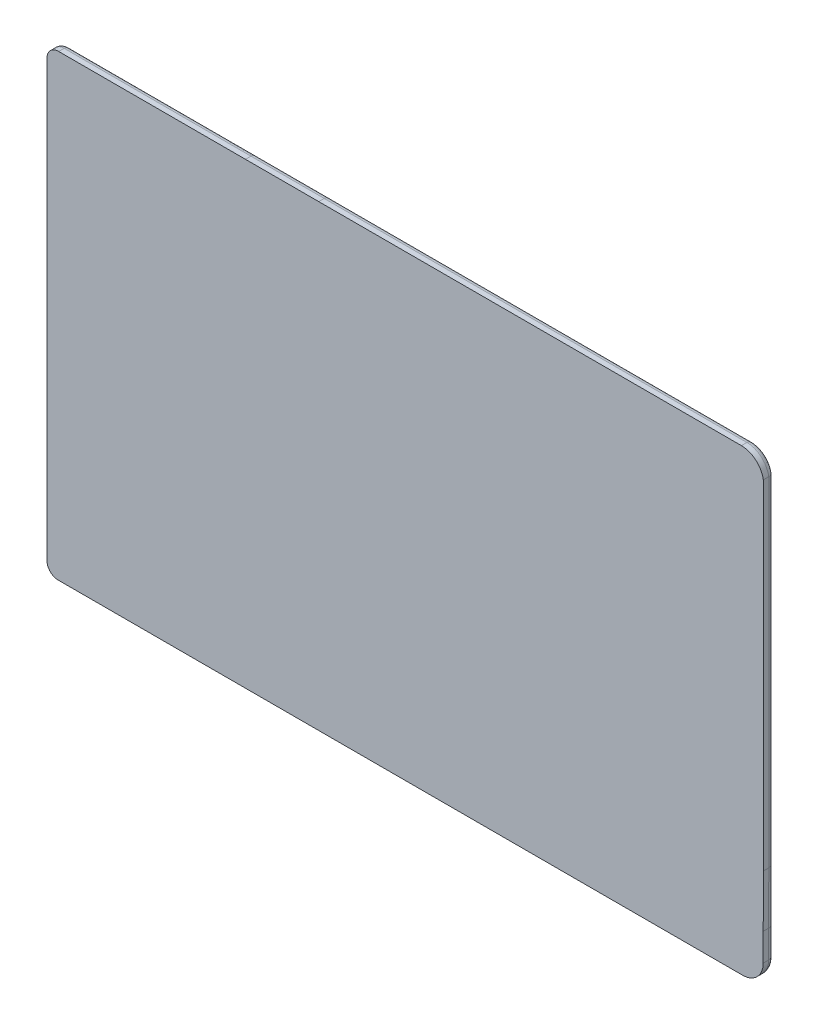
SolidWorks part; units mm, degrees
ref_plane "Front Plane" through (0, 0, 0) normal (0, 0, 1) x (1, 0, 0)
ref_plane "Top Plane" through (0, 0, 0) normal (0, 1, 0) x (1, 0, 0)
ref_plane "Right Plane" through (0, 0, 0) normal (1, 0, 0) x (0, 0, -1)
sketch "Sketch1" plane through (0, 0, 0) normal (0, 0, 1) x (1, 0, 0)
  line L58 (-23.7559, 7.1563) -> (-23.7559, 15.1458)
  line L61 (-23.7559, -4.5467) -> (-23.7559, -52.7249)
  line L66 (-23.7559, -57.433) -> (-23.7559, -64.4373)
  line L67 (-21.7197, -66.498) -> (103.2421, -66.498)
  line L69 (107.2324, -62.6937) -> (107.2324, -57.648)
  line L71 (107.2421, -48.1039) -> (107.2421, -39.782)
  line L74 (12.5461, 17.2703) -> (-21.6069, 17.2703)
  line L77 (107.2421, -33.7922) -> (107.2421, -20.0797)
  line L78 (107.2421, -4.5797) -> (107.2421, 13.8581)
  line L80 (-21.6069, 16.5996) -> (-21.6069, 16.5962)
  line L85 (25.9461, 17.2719) -> (103.2421, 17.2719)
  line L87 (107.2421, -20.0797) -> (107.2421, -4.5797)
  line L89 (107.2324, -57.648) -> (107.2421, -48.1039)
  line L90 (107.2421, -33.7922) -> (107.2421, -39.782)
  line L91 (-23.7559, -52.7249) -> (-23.7559, -57.433)
  line L92 (-23.7559, 7.1563) -> (-23.7559, -4.5467)
  line L93 (12.5461, 17.2703) -> (25.9461, 17.2719)
  arc A9 (-23.7559, 15.1458) -> (-21.6069, 17.2703) centre (-21.6313, 15.1458) cw
  arc A11 (103.2421, 17.2719) -> (107.2421, 13.8581) centre (103.2421, 13.2216) cw
  arc A13 (107.2324, -62.6937) -> (103.2421, -66.498) centre (103.4238, -62.6937) cw
  arc A15 (-23.7559, -64.4373) -> (-21.7197, -66.498) centre (-21.6951, -64.4373) ccw
extrude "Boss-Extrude1" add sketch "Sketch1" along normal blind 2 contours L66 A15 L67 A13 L69 L89 L71 L90 L77 L87 L78 A11 L85 L93 L74 A9 L58 L92 L61 L91 region at (41.7158, -24.614, 0)
fillet "Fillet1" radius 1 12 edges at (-23.161, -65.8858, 0) (40.7612, -66.498, 0) (106.0519, -65.4503, 0) (107.2324, -60.1708, 0) (107.2372, -52.8759, 0) (107.2421, -17.1229, 0) (105.8714, 16.3024, 0) (64.5941, 17.2719, 0) (19.2461, 17.2711, 0) (-4.5304, 17.2703, 0) (-23.125, 16.6568, 0) (-23.7559, -24.6457, 0)
